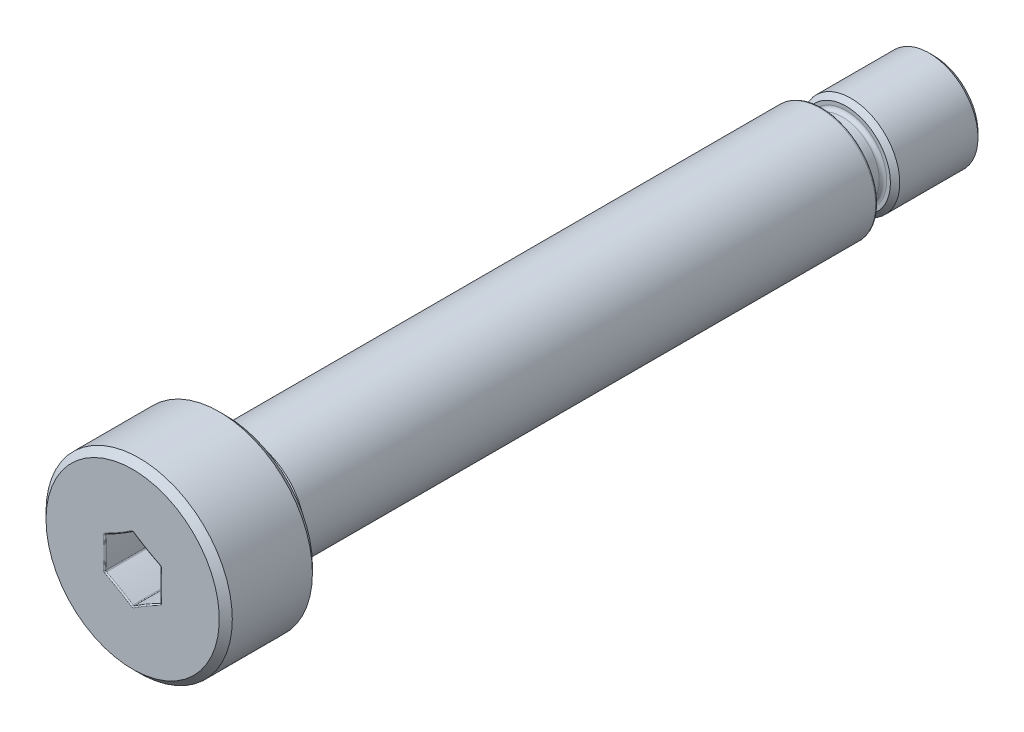
SolidWorks part; units mm, degrees
material "Alloy Steel (SS)"
ref_plane "Front Plane" through (0, 0, 0) normal (0, 0, 1) x (1, 0, 0)
ref_plane "Top Plane" through (0, 0, 0) normal (0, 1, 0) x (1, 0, 0)
ref_plane "Right Plane" through (0, 0, 0) normal (1, 0, 0) x (0, 0, -1)
sketch "Sketch1" plane through (0, 0, 0) normal (0, 0, 1) x (1, 0, 0)
  line L1 (1.1906, 0.6874) -> (0, 1.3748)
  line L2 (0, 1.3748) -> (-1.1906, 0.6874)
  line L3 (-1.1906, 0.6874) -> (-1.1906, -0.6874)
  line L4 (-1.1906, -0.6874) -> (0, -1.3748)
  line L5 (0, -1.3748) -> (1.1906, -0.6874)
  line L6 (1.1906, -0.6874) -> (1.1906, 0.6874)
  circle A0 centre (0, 0) radius 3.9688
  circle A1 centre (0, 0) radius 2.3813
  circle A2 centre (0, 0) radius 2.0828
  circle A3 centre (0, 0) radius 1.1906 construction
  dimension "Head Diameter" = 7.9375
  dimension "Shoulder Diameter" = 4.7625
  dimension "Screw Size Decimal Equivalent" = 4.1656
  dimension "Drive Size" = 2.3813
sketch "Sketch2" plane through (0, 0, 0) normal (1, 0, 0) x (0, 0, -1)
  line L0 (30.1625, 2.0828) -> (0, 2.0828) construction
  line L1 (0, 3.9688) -> (-3.9688, 3.9687) construction
  line L2 (25.4, 2.3813) -> (0, 2.3813) construction
  line L3 (0, -3.9688) -> (-3.9688, -3.9688) construction
  line L6 (0, -2.0828) -> (30.1625, -2.0828) construction
  line L9 (30.1129, 2.1687) -> (30.9066, 2.1687) construction
  line L10 (30.9066, 2.1687) -> (30.5098, 1.4813) construction
  line L11 (30.5098, 1.4813) -> (30.1129, 2.1687) construction
  line L12 (30.1625, 2.0828) -> (30.857, 2.0828) construction
  line L13 (30.4602, 1.5672) -> (30.5594, 1.5672) construction
  line L14 (30.5098, 1.5672) -> (30.5098, 1.4813) construction
  line L15 (30.5098, 2.1687) -> (30.5098, 2.0828) construction
  line L16 (30.1377, 2.1258) -> (30.8818, 2.1258) construction
  line L17 (-3.9688, 0) -> (30.1625, 0) construction
  line L18 (25.4, 2.3813) -> (25.4, -2.0828) construction
  point P23 (30.5098, 2.1258)
  point P24 (29.3687, 2.0828)
  dimension "Head Height" = 3.9688
  dimension "Shoulder Length" = 25.4
  dimension "Thread Length" = 4.7625
  dimension "Thread Pitch" = 0.7937
  dimension "D2" = 0.0992
  dimension "Thread Note" = 0.7937
sketch "Sketch3" plane through (0, 0, 0) normal (1, 0, 0) x (0, 0, -1)
  line L0 (-3.9688, 3.9687) -> (0, 3.9688)
  line L1 (0, 3.9688) -> (0, 2.3813)
  line L2 (0, 2.3813) -> (25.4, 2.3813)
  line L3 (25.4, 2.3813) -> (25.4, 2.0828)
  line L4 (30.1625, 2.0828) -> (0, 2.0828) construction
  line L5 (25.4, 2.0828) -> (30.1625, 2.0828)
  line L6 (30.1625, 2.0828) -> (30.1625, 0)
  line L7 (30.1625, 0) -> (-3.9688, 0)
  line L8 (-3.9688, 0) -> (-3.9688, 3.9687)
  line L9 (-3.9688, 0) -> (30.1625, 0) construction
revolve "Revolve1" add sketch "Sketch3" angle 360 about L17
sketch "Sketch4" plane through (0, 0, 0) normal (1, 0, 0) x (0, 0, -1)
  line L0 (-3.9688, 0) -> (30.1625, 0) construction
  line L1 (0, 2.3813) -> (0.9922, 2.3813)
  line L2 (0, 2.3813) -> (0, 2.0241)
  line L3 (0, 2.0241) -> (0.9922, 2.0241)
  line L4 (0.9922, 2.3813) -> (0.9922, 2.0241)
  line L5 (30.1625, 2.0828) -> (0, 2.0828) construction
  line L6 (25.4, 2.0828) -> (26.4319, 2.0828)
  line L7 (25.4, 2.0828) -> (25.4, 1.5672)
  line L8 (25.4, 1.5672) -> (26.4319, 1.5672)
  line L9 (26.4319, 2.0828) -> (26.4319, 1.5672)
  line L10 (30.4602, 1.5672) -> (30.5594, 1.5672) construction
  line L12 (12.7, 2.3813) -> (12.7, 0) construction
  line L13 (25.4, 2.3813) -> (0, 2.3813) construction
  point P22 (2.163, 2.0241)
  point P23 (23.237, 2.0241)
  dimension "D1" = 0.9922
  dimension "D2" = 4.0481
  dimension "D3" = 1.0319
  dimension "D4" = 21.0741
revolve "Cut-Revolve1" cut sketch "Sketch4" angle 360 about L17
chamfer "Chamfer1" distance 0.3572 angle 45 1 edges at (2.0241, 0, -0.9922)
fillet "Fillet1" radius 0.1786 1 edges at (2.0241, 0, 0)
fillet "Fillet2" radius 0.1588 2 edges at (1.5672, 0, -25.4) (1.5672, 0, -26.4319)
chamfer "Chamfer2" distance 0.1984 angle 45 2 edges at (2.0828, 0, -26.4319) (2.0828, 0, -30.1625)
fillet "Fillet3" radius 0.0953 1 edges at (2.3813, 0, -25.4)
chamfer "Chamfer3" distance 0.2778 angle 45 2 edges at (3.9688, 0, 0) (3.9687, 0, 3.9688)
sketch "Sketch5" plane through (0, 0, 3.9688) normal (0, 0, 1) x (1, 0, 0)
  arc A0 (1.1906, 0.6874) -> (0, 1.3748) centre (5.5503, 9.6134) cw
  circle A2 centre (0, 0) radius 1.1668 construction
  arc A3 (1.1906, -0.6874) -> (1.1906, 0.6874) centre (11.1006, 0) cw
  arc A4 (0, -1.3748) -> (1.1906, -0.6874) centre (5.5503, -9.6134) cw
  arc A5 (-1.1906, -0.6874) -> (0, -1.3748) centre (-5.5503, -9.6134) cw
  arc A6 (-1.1906, 0.6874) -> (-1.1906, -0.6874) centre (-11.1006, 0) cw
  arc A7 (0, 1.3748) -> (-1.1906, 0.6874) centre (-5.5503, 9.6134) cw
  point P25 (0, 0)
  dimension "D1" = 2.3336
  dimension "D2" = 6
extrude "Cut-Extrude1" cut sketch "Sketch5" against normal blind 2.0828
fillet "Fillet4" radius 0.0508 18 edges at (1.1668, 0, 3.9688) (1.1906, -0.6874, 2.9274) (0.5834, -1.0105, 3.9688) (0, -1.3748, 2.9274) (-0.5834, -1.0105, 3.9688) (-1.1906, -0.6874, 2.9274) (-1.1668, 0, 3.9688) (-1.1906, 0.6874, 2.9274) (-0.5834, 1.0105, 3.9688) (1.1906, 0.6874, 2.9274) (0, 1.3748, 2.9274) (0.5834, 1.0105, 3.9688) (0.5834, -1.0105, 1.886) (-0.5834, -1.0105, 1.886) (-1.1668, 0, 1.886) (-0.5834, 1.0105, 1.886) (0.5834, 1.0105, 1.886) (1.1668, 0, 1.886)
sketch "Sketch6" [suppressed] plane through (0, 0, -30.1625) normal (0, 0, -1) x (-1, 0, 0)
  circle A0 centre (0, 0) radius 2.0828
  circle A1 centre (0, 0) radius 2.0828 construction
sketch "Sketch7" [suppressed] plane through (0, 0, 0) normal (1, 0, 0) x (0, 0, -1)
  line L0 (30.1377, 2.1258) -> (30.8818, 2.1258)
  line L1 (30.8818, 2.1258) -> (30.5594, 1.5672)
  line L2 (30.5594, 1.5672) -> (30.4602, 1.5672)
  line L3 (30.4602, 1.5672) -> (30.1377, 2.1258)
other "DeleteFace1" [suppressed]
curve "Helix/Spiral1" [suppressed] pitch 0.7937 height 4.3497 turns 5.48
sweep "Cut-Sweep1" [suppressed] cut profiles "Sketch7" path "Helix/Spiral1"
equation "\"D2@Sketch2\" = \"Thread Pitch@Sketch2\" / 8"
equation "\"D1@Sketch4\" = \"Head Height@Sketch2\" * .25"
equation "\"D3@Sketch4\" = \"Thread Pitch@Sketch2\" * 1.3"
equation "\"D2@Sketch4\" = \"Shoulder Diameter@Sketch1\" * .85"
equation "\"D1@Chamfer1\" =  ( \"Shoulder Diameter@Sketch1\" - \"D2@Sketch4\" )  * .5"
equation "\"D1@Fillet1\"=\"d1@chaMFER1\"*.5"
equation "\"D1@Fillet2\"=\"Thread Pitch@Sketch2\"*.2"
equation "\"D1@Chamfer2\"=\"Thread Pitch@Sketch2\"*.25"
equation "\"D1@Fillet3\"=\"Shoulder Diameter@Sketch1\"*.02"
equation "\"D1@Chamfer3\" = \"Head Height@Sketch2\" * .07"
equation "\"D1@Sketch5\"=\"Drive Size@Sketch1\"*.98"
equation "\"D1@Cut-Extrude1\"=\"Screw Size Decimal Equivalent@Sketch1\"*.5"
equation "\"D4@Helix/Spiral1\"=\"thread pitch@sketch2\""
equation "\"D3@Helix/Spiral1\"=\"Thread Length@Sketch2\" - \"D3@Sketch4\" * .4"
equation "\"D4@Sketch4\"=(\"Shoulder Length@Sketch2\"-(2*\"D1@Sketch4\"))*.9"
equation "\"Thread Note@Sketch2\"=\"Thread Pitch@Sketch2\" * 1"
